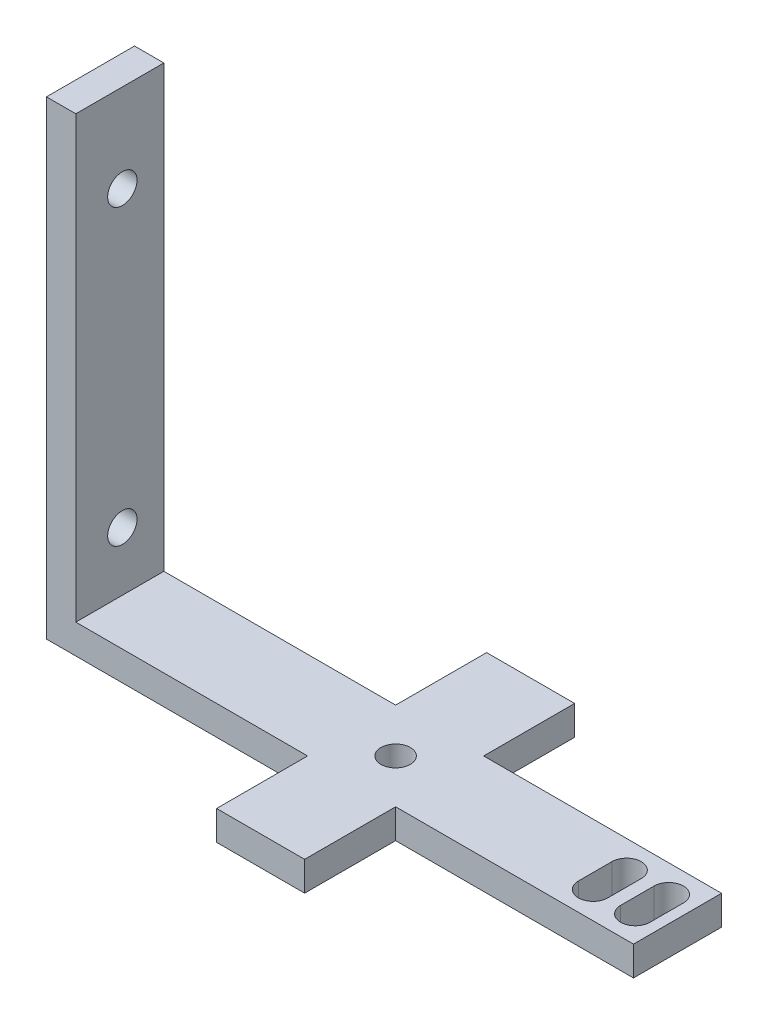
SolidWorks part; units mm, degrees
ref_plane "Front Plane" through (0, 0, 0) normal (0, 0, 1) x (1, 0, 0)
ref_plane "Top Plane" through (0, 0, 0) normal (0, 1, 0) x (1, 0, 0)
ref_plane "Right Plane" through (0, 0, 0) normal (1, 0, 0) x (0, 0, -1)
sketch "Sketch1" plane through (0, 0, 0) normal (0, 1, 0) x (1, 0, 0)
  line L1 (-53.3412, 17.0332) -> (46.6588, 17.0332)
  line L2 (-53.3412, 17.0332) -> (-53.3412, 2.0332)
  line L3 (-53.3412, 2.0332) -> (46.6588, 2.0332)
  line L4 (46.6588, 17.0332) -> (46.6588, 2.0332)
  dimension "D1" = 100
  dimension "D2" = 15
extrude "Boss-Extrude1" add sketch "Sketch1" along normal blind 5
sketch "Sketch2" plane through (0, 5, 0) normal (0, 1, 0) x (1, 0, 0)
  line L0 (-53.3412, 17.0332) -> (-48.3412, 17.0332)
  line L1 (46.6588, 17.0332) -> (-53.3412, 17.0332) construction
  line L2 (-53.3412, 2.0332) -> (-48.3412, 2.0332)
  line L3 (-53.3412, 2.0332) -> (46.6588, 2.0332) construction
  line L4 (-48.3412, 17.0332) -> (-48.3412, 2.0332)
  line L5 (-53.3412, 17.0332) -> (-53.3412, 2.0332)
extrude "Boss-Extrude2" add sketch "Sketch2" along normal blind 75
sketch "Sketch3" plane through (0, 0, 0) normal (0, -1, 0) x (-1, 0, 0)
  line L0 (53.3412, 2.0332) -> (1.3612, 2.0332) construction
  line L1 (53.3412, 2.0332) -> (-46.6588, 2.0332) construction
  line L2 (1.3612, 2.0332) -> (1.3612, -8.4668) construction
  line L3 (8.8612, 17.0332) -> (8.8612, 32.5332)
  line L5 (-46.6588, 17.0332) -> (53.3412, 17.0332) construction
  line L6 (8.8612, 32.5332) -> (-6.1388, 32.5332)
  line L8 (-6.1388, 32.5332) -> (-6.1388, 17.0332)
  line L9 (-6.1388, 17.0332) -> (8.8612, 17.0332)
  line L15 (1.3612, 2.0332) -> (8.8612, 2.0332)
  line L16 (1.3612, 2.0332) -> (-6.1388, 2.0332)
  line L17 (8.8612, 2.0332) -> (8.8612, -13.4668)
  line L18 (-6.1388, 2.0332) -> (-6.1388, -13.4668)
  line L19 (-6.1388, -13.4668) -> (8.8612, -13.4668)
  line M5 (53.3412, 17.0332) -> (-46.6588, 17.0332)
  line M7 (-46.6588, 2.0332) -> (53.3412, 2.0332)
extrude "Boss-Extrude3" add sketch "Sketch3" against normal blind 5 contours L8 L6 M5 | L19 M7 region at (-1.3612, 0, -24.7832) region at (-1.3612, 0, 5.7168)
sketch "Sketch4" plane through (0, 0, 0) normal (0, -1, 0) x (-1, 0, 0)
  line L0 (-46.6588, 9.5332) -> (53.3412, 9.5332)
  line L1 (-46.6588, 2.0332) -> (-46.6588, 17.0332) construction
  line L2 (53.3412, 17.0332) -> (53.3412, 2.0332) construction
sketch "Sketch5" plane through (-53.3412, 0, 0) normal (-1, 0, 0) x (0, 0, 1)
  line L0 (-9.5332, 0) -> (-9.5332, 15)
  line L1 (-17.0332, 0) -> (-2.0332, 0) construction
  line L2 (-9.5332, 80) -> (-9.5332, 65)
  line L3 (-17.0332, 80) -> (-2.0332, 80) construction
hole_wizard "Ø5.0mm Dowel Slot1" positions "Sketch6" profile "Sketch7" size "Ø5.0" standard "ANSI Metric" slot yes end condition up to next
sketch "Sketch6" plane through (0, 5, 0) normal (0, 1, 0) x (1, 0, 0)
  line L0 (42.3428, 4.1592) -> (42.3428, 14.8592) construction
  point P0 (42.3428, 9.5092)
  point P5 (42.3428, 14.8592)
  dimension "D1" = 10.7
sketch "Sketch7" plane through (42.3428, 5, -9.5092) normal (1, 0, 0) x (0, 0, 1)
  line L0 (0, 0) -> (0, 5)
  line L1 (0, 5) -> (2.5, 5)
  line L2 (2.5, 5) -> (2.5, 0)
  line L5 (2.5, 0) -> (0, 0)
  line L11 (0, -6.35) -> (0, 107.95) construction
  dimension "Thru Hole Dia." = 5
  dimension "Thru Hole Depth" = 5
hole_wizard "Ø5.0mm Dowel Slot2" positions "Sketch8" profile "Sketch9" size "Ø5.0" standard "ANSI Metric" slot yes end condition up to next
sketch "Sketch8" plane through (0, 0, 0) normal (0, -1, 0) x (-1, 0, 0)
  line L0 (-35.1546, 4.1648) -> (-35.1546, 14.8648) construction
  point P0 (-35.1546, 9.5148)
  point P6 (-35.1546, 14.8648)
  dimension "D1" = 10.7
sketch "Sketch9" plane through (35.1546, 0, -9.5148) normal (1, 0, 0) x (0, 0, -1)
  line L0 (0, 0) -> (0, 5)
  line L1 (0, 5) -> (2.5, 5)
  line L2 (2.5, 5) -> (2.5, 0)
  line L5 (2.5, 0) -> (0, 0)
  line L11 (0, -6.35) -> (0, 107.95) construction
  dimension "Thru Hole Dia." = 5
  dimension "Thru Hole Depth" = 5
hole_wizard "Ø5.0mm Dowel Hole1" positions "Sketch10" profile "Sketch11" hole size "Ø5.0" standard "ANSI Metric" end condition up to next
sketch "Sketch10" plane through (-53.3412, 0, 0) normal (-1, 0, 0) x (0, 0, 1)
  point P0 (-9.9586, 65)
  point P3 (-9.9586, 15)
sketch "Sketch11" plane through (-53.3412, 65, -9.9586) normal (0, 1, 0) x (0, 0, 1)
  line L0 (0, 0) -> (0, 5)
  line L1 (0, 5) -> (2.5, 5)
  line L2 (2.5, 5) -> (2.5, 0)
  line L5 (2.5, 0) -> (0, 0)
  line L11 (0, -6.35) -> (0, 107.95) construction
  dimension "Thru Hole Dia." = 5
  dimension "Thru Hole Depth" = 5
sketch "Sketch12" plane through (0, 5, 0) normal (0, 1, 0) x (1, 0, 0)
  line L0 (-1.3612, 32.5332) -> (-1.3612, -13.4668)
  line L1 (-8.8612, 32.5332) -> (6.1388, 32.5332) construction
  line L2 (6.1388, -13.4668) -> (-8.8612, -13.4668) construction
  line L3 (-1.3612, -13.4668) -> (-1.3612, 9.5332)
  line L4 (-1.3612, 9.5332) -> (-8.8612, 9.5332)
hole_wizard "Ø5.0mm Dowel Hole2" positions "Sketch13" profile "Sketch14" hole size "Ø5.0" standard "ANSI Metric" end condition up to next
sketch "Sketch13" plane through (0, 5, 0) normal (0, 1, 0) x (1, 0, 0)
  point P0 (-1.3612, 9.5332)
sketch "Sketch14" plane through (-1.3612, 5, -9.5332) normal (1, 0, 0) x (0, 0, 1)
  line L0 (0, 0) -> (0, 5)
  line L1 (0, 5) -> (2.5, 5)
  line L2 (2.5, 5) -> (2.5, 0)
  line L5 (2.5, 0) -> (0, 0)
  line L11 (0, -6.35) -> (0, 107.95) construction
  dimension "Thru Hole Dia." = 5
  dimension "Thru Hole Depth" = 5
